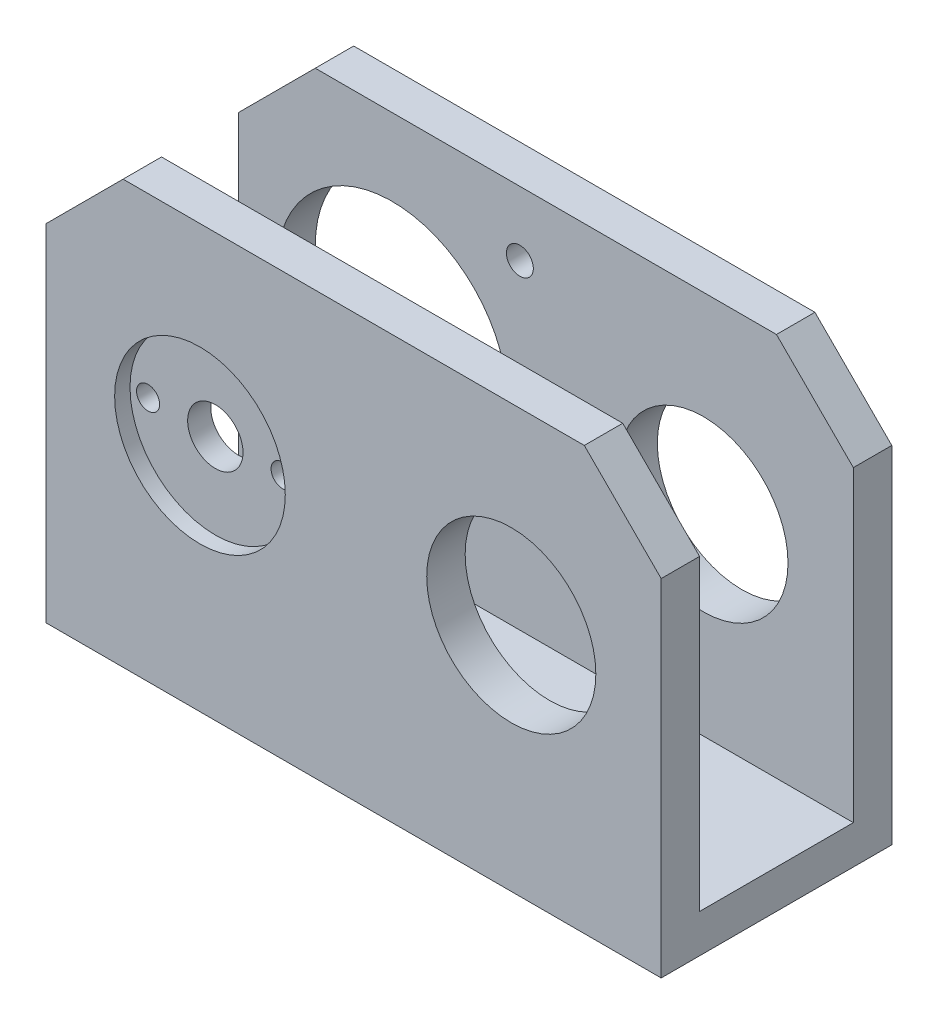
SolidWorks part; units mm, degrees
ref_plane "Front Plane" through (0, 0, 0) normal (0, 0, 1) x (1, 0, 0)
ref_plane "Top Plane" through (0, 0, 0) normal (0, 1, 0) x (1, 0, 0)
ref_plane "Right Plane" through (0, 0, 0) normal (1, 0, 0) x (0, 0, -1)
sketch "Sketch1" plane through (0, 0, 0) normal (0, 0, 1) x (1, 0, 0)
  line L1 (-120, 24) -> (-40, 24)
  line L2 (-120, 24) -> (-120, -26)
  line L3 (-120, -26) -> (-40, -26)
  line L4 (-40, 24) -> (-40, -26)
  dimension "D1" = 50
  dimension "D2" = 80
extrude "Boss-Extrude1" add sketch "Sketch1" along normal blind 5
sketch "Sketch2" plane through (0, 0, 5) normal (0, 0, 1) x (1, 0, 0)
  line L0 (-120, -26) -> (-40, -26) construction
  line L2 (-120, 24) -> (-120, -26) construction
  circle A0 centre (-100, -1) radius 3.6
  dimension "D1" = 7.2
  dimension "D2" = 25
  dimension "D3" = 20
extrude "Cut-Extrude1" cut sketch "Sketch2" against normal through all
sketch "Sketch3" plane through (0, 0, 5) normal (0, 0, 1) x (1, 0, 0)
  line L0 (-100, 2.6) -> (-100, -1) construction
  line L1 (-100, -1) -> (-96.4, -1) construction
  circle A0 centre (-91.25, -1) radius 1.5
  circle A1 centre (-100, -1) radius 3.6 construction
  circle A2 centre (-108.75, -1) radius 1.5
  dimension "D2" = 3
  dimension "D3" = 17.5
extrude "Cut-Extrude2" cut sketch "Sketch3" against normal through all contours A2 | A0
sketch "Sketch4" plane through (0, 0, 5) normal (0, 0, 1) x (1, 0, 0)
  circle A0 centre (-100, -1) radius 11.1
  circle A1 centre (-100, -1) radius 3.6 construction
  dimension "D1" = 22.2
extrude "Cut-Extrude3" cut sketch "Sketch4" against normal blind 2
sketch "Sketch5" plane through (0, 0, 5) normal (0, 0, 1) x (1, 0, 0)
  line L0 (-108.75, -1) -> (-27.4836, -1) construction
  circle A0 centre (-59.5, -1) radius 11
  circle A1 centre (-100, -1) radius 3.6 construction
  dimension "D1" = 22
  dimension "D2" = 40.5
extrude "Cut-Extrude4" cut sketch "Sketch5" against normal through all
sketch "Sketch7" plane through (0, -26, 0) normal (0, -1, 0) x (1, 0, 0)
  line L1 (-120, -25) -> (-40, -25)
  line L2 (-120, -25) -> (-120, 5)
  line L3 (-120, 5) -> (-40, 5)
  line L4 (-40, -25) -> (-40, 5)
  line L5 (-120, 5) -> (-40, 5) construction
  line L6 (-40, 5) -> (-40, 0) construction
  point P6 (-40, 0)
  dimension "D1" = 30
  dimension "D2" = 80
extrude "Boss-Extrude2" add sketch "Sketch7" along normal blind 5
sketch "Sketch9" plane through (-40, 0, 0) normal (1, 0, 0) x (0, 0, -1)
  line L1 (12.5, -31.5471) -> (12.5, -20.4529) construction
  line L3 (25, -26) -> (0, -26) construction
  point P0 (10, -12.2692)
  point P4 (12.5, -26)
  point P6 (0, 0)
  point P7 (0, 0)
  point P8 (0, 0)
  point P9 (0, 0)
  point P10 (0, 0)
  point P11 (8.7462, -12.2692)
  dimension "D1" = 2.5
ref_axis "Axis1" through (-40, -31, -10) along (-1, 0, 0)
ref_plane "Plane3" through (0, 0, -10) normal (0, 0, -1) x (-1, 0, 0)
sketch "Sketch11" plane through (0, -31, 0) normal (0, -1, 0) x (1, 0, 0)
  line L0 (-80, 5) -> (-80, -25) construction
  line L1 (-40, 5) -> (-120, 5) construction
  line L2 (-120, -25) -> (-40, -25) construction
sketch "Sketch12" plane through (0, 0, 5) normal (0, 0, 1) x (1, 0, 0)
  line L0 (-80, 24) -> (-80, -31) construction
  line L1 (-40, 24) -> (-120, 24) construction
  line L2 (-40, -31) -> (-120, -31) construction
ref_plane "Plane4" through (-80, 0, 0) normal (1, 0, 0) x (0, 0, -1)
sketch "Sketch13" plane through (0, -26, 0) normal (0, 1, 0) x (1, 0, 0)
  line L0 (-40, 25) -> (-40, 0) construction
  line L1 (-120, 25) -> (-40, 25)
  line L2 (-120, 25) -> (-120, 20)
  line L3 (-120, 20) -> (-40, 20)
  line L4 (-40, 25) -> (-40, 20)
  dimension "D1" = 5
extrude "Boss-Extrude3" add sketch "Sketch13" along normal up to surface (50 mm away) up to face at (-80, 24, 2.5)
sketch "Sketch14" plane through (0, 0, -25) normal (0, 0, -1) x (-1, 0, 0)
  circle A0 centre (100, -1) radius 15
  circle A1 centre (100, -1) radius 3.6 construction
  dimension "D1" = 30
  dimension "D2" = 7.2
  dimension "D3" = 7.2
extrude "Cut-Extrude6" cut sketch "Sketch14" against normal up to next contours A0
sketch "Sketch16" plane through (0, 0, -25) normal (0, 0, -1) x (-1, 0, 0)
  line L0 (83.383, 15.617) -> (116.617, -17.617) construction
  line L1 (91.25, -1) -> (108.75, -1) construction
  circle A0 centre (100, -1) radius 3.6 construction
  circle A1 centre (83.383, 15.617) radius 1.75
  circle A2 centre (116.617, -17.617) radius 1.75
  point P4 (100, -1)
  dimension "D3" = 3.5
  dimension "D4" = 3.5
  dimension "D1" = 135
  dimension "D2" = 23.5
extrude "Cut-Extrude7" cut sketch "Sketch16" against normal up to next
mirror "Mirror6" about plane through (0, 0, -10) normal (0, 0, -1) of "Cut-Extrude4"
chamfer "Chamfer1" distance 10 angle 45 4 edges at (-120, 24, 2.5) (-120, 24, -22.5) (-40, 24, 2.5) (-40, 24, -22.5)
